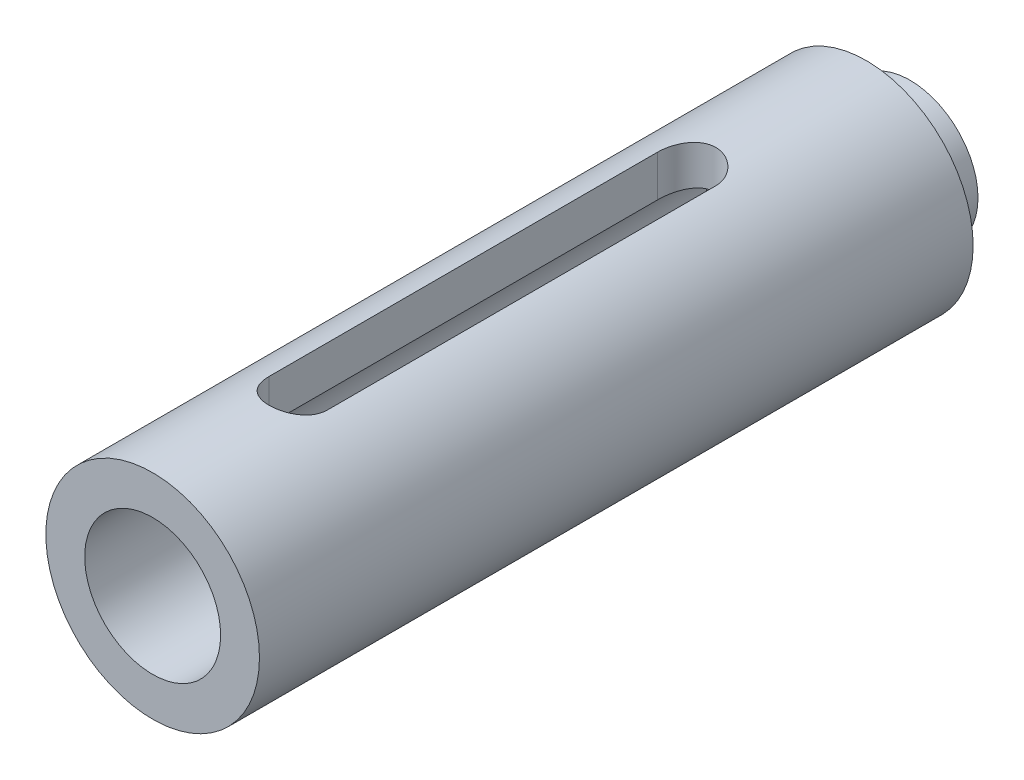
SolidWorks part; units mm, degrees
material "Zinc AC41A Alloy, As Cast"
ref_plane "Plan de face" through (0, 0, 0) normal (0, 0, 1) x (1, 0, 0)
ref_plane "Plan de dessus" through (0, 0, 0) normal (0, 1, 0) x (1, 0, 0)
ref_plane "Plan de droite" through (0, 0, 0) normal (1, 0, 0) x (0, 0, -1)
sketch "Sketch1" plane through (0, 0, 0) normal (0, 0, 1) x (1, 0, 0)
  circle A0 centre (0, 0) radius 3.5
  dimension "D1" = 7
extrude "Boss-Extrude1" add sketch "Sketch1" along normal blind 2.25
sketch "Sketch2" plane through (0, 0, 2.25) normal (0, 0, 1) x (1, 0, 0)
  circle A0 centre (0, 0) radius 5.5
  dimension "D1" = 11
extrude "Boss-Extrude2" add sketch "Sketch2" along normal blind 36.75
sketch "Sketch3" plane through (0, 0, 39) normal (0, 0, 1) x (1, 0, 0)
  circle A0 centre (0, 0) radius 3.5
  dimension "D1" = 7
extrude "Cut-Extrude1" cut sketch "Sketch3" against normal blind 33
sketch "Sketch4" plane through (0, 0, 0) normal (0, 0, -1) x (-1, 0, 0)
  circle A0 centre (0, 0) radius 2
  dimension "D1" = 4
extrude "Cut-Extrude2" cut sketch "Sketch4" against normal up to next
cosmetic thread "Cosmetic Thread1" parameters "D2"=5
chamfer "Chamfer1" distance 1 distance2 1.5 1 edges at (3.5, 0, 6) first distance on face at (3.5, 0, 6)
sketch "Sketch5" plane through (0, 0, 0) normal (0, 1, 0) x (1, 0, 0)
  line L0 (-1.5, -31.5) -> (1.5, -31.5) construction
  line L1 (-1.5, -11.5) -> (1.5, -11.5) construction
  line L2 (-1.5, -11.5) -> (-1.5, -31.5)
  line L3 (1.5, -11.5) -> (1.5, -31.5)
  line L4 (0, 0) -> (0, -11.5) construction
  arc A0 (1.5, -11.5) -> (-1.5, -11.5) centre (0, -11.5) ccw
  arc A1 (-1.5, -31.5) -> (1.5, -31.5) centre (0, -31.5) ccw
  point P1 (0, 0)
  point P3 (0, 0)
  point P5 (0, 0)
  dimension "D1" = 20
  dimension "D3" = 3
  dimension "D4" = 3
  dimension "D5" = 1.5
  dimension "D2" = 11.5
extrude "Cut-Extrude3" cut sketch "Sketch5" along normal through all
